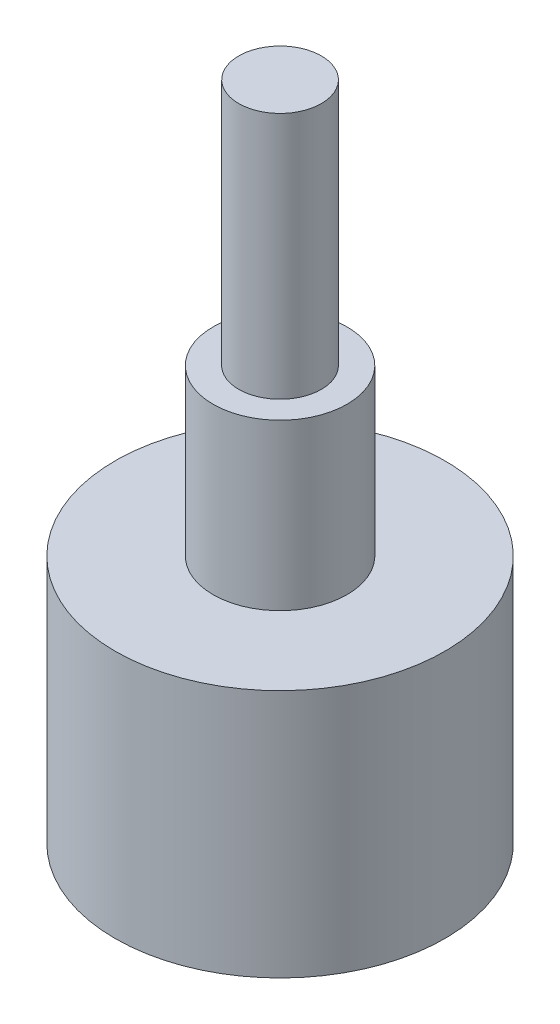
SolidWorks part; units mm, degrees
ref_plane "Front Plane" through (0, 0, 0) normal (0, 0, 1) x (1, 0, 0)
ref_plane "Top Plane" through (0, 0, 0) normal (0, 1, 0) x (1, 0, 0)
ref_plane "Right Plane" through (0, 0, 0) normal (1, 0, 0) x (0, 0, -1)
sketch "Sketch1" plane through (0, 0, 0) normal (0, 1, 0) x (1, 0, 0)
  circle A0 centre (0, 0) radius 6.35
extrude "Boss-Extrude1" add sketch "Sketch1" along normal blind 9.58
sketch "Sketch4" plane through (0, 9.58, 0) normal (0, 1, 0) x (1, 0, 0)
  circle A0 centre (0, 0) radius 2.58
extrude "Boss-Extrude2" add sketch "Sketch4" along normal blind 6.35
sketch "Sketch5" plane through (0, 15.93, 0) normal (0, 1, 0) x (1, 0, 0)
  circle A0 centre (0, 0) radius 1.59
extrude "Boss-Extrude3" add sketch "Sketch5" along normal blind 9.53
